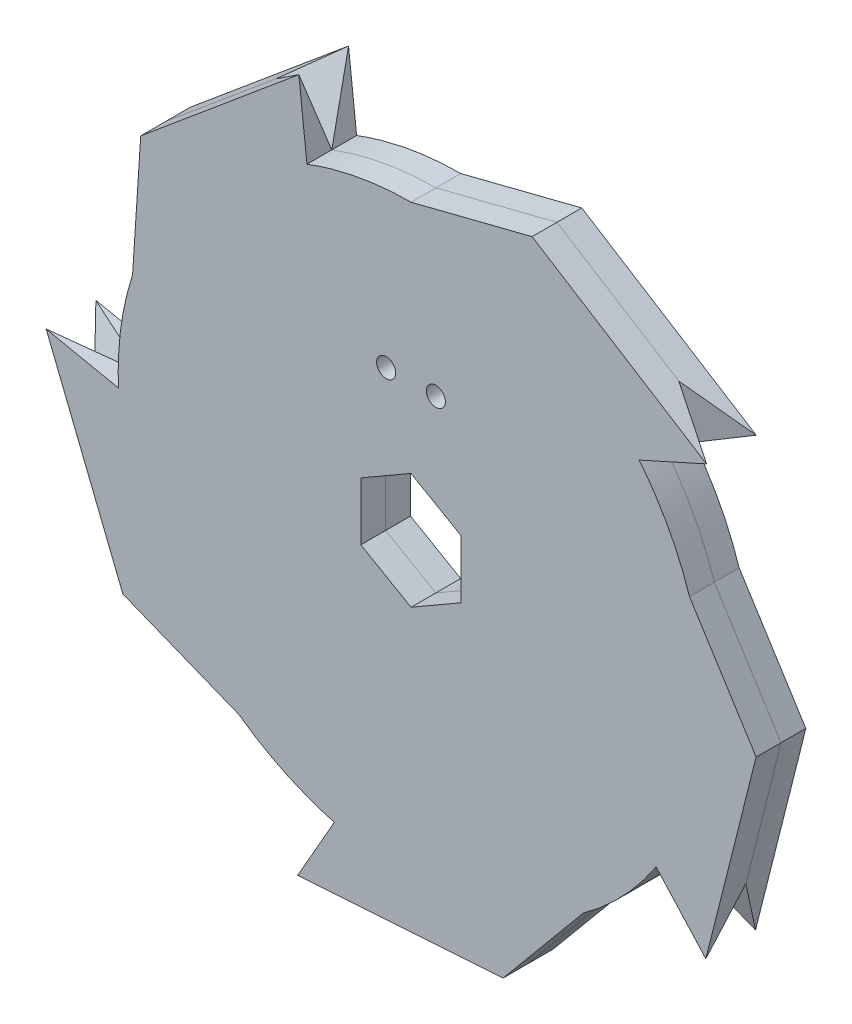
SolidWorks part; units mm, degrees
material "Plain Carbon Steel"
ref_plane "Front Plane" through (0, 0, 0) normal (0, 0, 1) x (1, 0, 0)
ref_plane "Top Plane" through (0, 0, 0) normal (0, 1, 0) x (1, 0, 0)
ref_plane "Right Plane" through (0, 0, 0) normal (1, 0, 0) x (0, 0, -1)
sketch "Sketch1" plane through (0, 0, 0) normal (0, 0, 1) x (1, 0, 0)
  line L0 (0, 19.8349) -> (8.2013, 21.9165)
  line L7 (8.2013, 21.9165) -> (20.0184, 14.4926)
  line L8 (15.4538, 12.4338) -> (20.0184, 14.4926)
  line L9 (18.8641, 6.1293) -> (23.3781, -1.0274)
  line L10 (23.3781, -1.0274) -> (19.9693, -14.5601)
  line L11 (16.6008, -10.8552) -> (19.9693, -14.5601)
  line L12 (11.6586, -16.0467) -> (6.2471, -22.5514)
  line L13 (6.2471, -22.5514) -> (-7.6767, -23.4912)
  line L14 (-5.194, -19.1427) -> (-7.6767, -23.4912)
  line L15 (-11.6586, -16.0467) -> (-19.5172, -12.9102)
  line L16 (-19.5172, -12.9102) -> (-24.7137, 0.0417)
  line L17 (-19.8108, -0.9756) -> (-24.7137, 0.0417)
  line L18 (-18.8641, 6.1293) -> (-18.3094, 14.5725)
  line L19 (-18.3094, 14.5725) -> (-7.5973, 23.517)
  line L20 (-7.0498, 18.5397) -> (-7.5973, 23.517)
  arc A2 (0, 19.8349) -> (-7.0498, 18.5397) centre (0, 0) ccw
  arc A3 (18.8641, 6.1293) -> (15.4538, 12.4338) centre (0, 0) ccw
  arc A4 (11.6586, -16.0467) -> (16.6008, -10.8552) centre (0, 0) ccw
  arc A5 (-11.6586, -16.0467) -> (-5.194, -19.1427) centre (0, 0) ccw
  arc A6 (-18.8641, 6.1293) -> (-19.8108, -0.9756) centre (0, 0) ccw
  dimension "D1" = 19.8349
  dimension "D3" = 8.4614
  dimension "D4" = 13.9555
  dimension "D5" = 5.0073
  dimension "D6" = 20.0184
  dimension "D7" = 17.1347
  dimension "D8" = 5
  dimension "D9" = 5
extrude "Boss-Extrude1" add sketch "Sketch1" along normal blind 6.35
scale "Scale1" scale about origin uniform scaling no x scale factor 1.886598 y scale factor 1.886598 z scale factor 1
sketch "Sketch2" plane through (0, 0, 6.35) normal (0, 0, 1) x (1, 0, 0)
  line L1 (7.3323, 0) -> (3.6662, 6.35)
  line L2 (3.6662, 6.35) -> (-3.6662, 6.35)
  line L3 (-3.6662, 6.35) -> (-7.3323, 0)
  line L4 (-7.3323, 0) -> (-3.6662, -6.35)
  line L5 (-3.6662, -6.35) -> (3.6662, -6.35)
  line L6 (3.6662, -6.35) -> (7.3323, 0)
  circle A0 centre (0, 0) radius 6.35 construction
  dimension "D1" = 12.7
extrude "Cut-Extrude1" [suppressed] cut sketch "Sketch2" against normal through all
sketch "Sketch3" plane through (0, 0, 6.35) normal (0, 0, 1) x (1, 0, 0)
  line L1 (6.4135, 3.7028) -> (0, 7.4057)
  line L2 (0, 7.4057) -> (-6.4135, 3.7028)
  line L3 (-6.4135, 3.7028) -> (-6.4135, -3.7028)
  line L4 (-6.4135, -3.7028) -> (0, -7.4057)
  line L5 (0, -7.4057) -> (6.4135, -3.7028)
  line L6 (6.4135, -3.7028) -> (6.4135, 3.7028)
  circle A0 centre (0, 0) radius 6.4135 construction
  dimension "D1" = 12.827
extrude "Cut-Extrude2" cut sketch "Sketch3" against normal through all
ref_axis "Axis1" through (0, 0, 4.0653) along (0, 0, 1)
sketch "Sketch4" [suppressed] plane through (0, 0, 6.35) normal (0, 0, 1) x (1, 0, 0)
  circle A0 centre (0, 17.526) radius 1.27
  dimension "D1" = 2.54
  dimension "D2" = 17.526
extrude "Cut-Extrude3" [suppressed] cut sketch "Sketch4" against normal through all
hole_wizard "#41 (0.096) Diameter Hole1" positions "Sketch5" profile "Sketch6" hole size "#41" standard "ANSI Inch" end condition up to next
sketch "Sketch5" plane through (0, 0, 6.35) normal (0, 0, 1) x (1, 0, 0)
  line L0 (-3.175, 17.526) -> (3.175, 17.526)
  point P0 (-3.175, 17.526)
  point P2 (3.175, 17.526)
  point P8 (0, 17.526)
  dimension "D1" = 6.35
  dimension "D2" = 17.526
sketch "Sketch6" plane through (-3.175, 17.526, 6.35) normal (1, 0, 0) x (0, -1, 0)
  line L0 (0, 0) -> (0, 6.35)
  line L1 (0, 6.35) -> (1.2192, 6.35)
  line L2 (1.2192, 6.35) -> (1.2192, 0)
  line L5 (1.2192, 0) -> (0, 0)
  line L11 (0, -6.35) -> (0, 107.95) construction
  dimension "Thru Hole Dia." = 2.4384
  dimension "Thru Hole Depth" = 6.35
ref_plane "Plane1" through (0, 0, 3.175) normal (0, 0, 1) x (1, 0, 0)
sketch "Sketch7" plane through (2.9122, -43.1444, 0) normal (0.0673, -0.9977, 0) x (0.9977, 0.0673, 0)
  line L0 (-17.4345, 6.35) -> (-9.497, 3.175)
  line L1 (-9.497, 3.175) -> (-17.4345, 0)
  line L2 (48.7771, 3.175) -> (-48.7771, 3.175) construction
  line L3 (-17.4345, 6.35) -> (-17.4345, 0)
  dimension "D1" = 7.9375
sketch "Sketch9" plane through (8.1599, -4.6586, 0) normal (-0.8684, 0.4958, 0) x (0, 0, 1)
  line L0 (6.35, -36.2215) -> (0, -36.2215) construction
  line L1 (3.175, -48.7771) -> (3.175, 48.7771) construction
  point P0 (3.175, -36.2215)
loft "Cut-Loft1" cut profiles "Sketch9", "Sketch7"
pattern_circular "CirPattern1" count 5 over 360 about axis through (0, 0, 4.0653) along (0, 0, 1) of "Cut-Loft1"
split "Split1" trim tools "Plane1" bodies to split 109 resulting bodies 110 111
